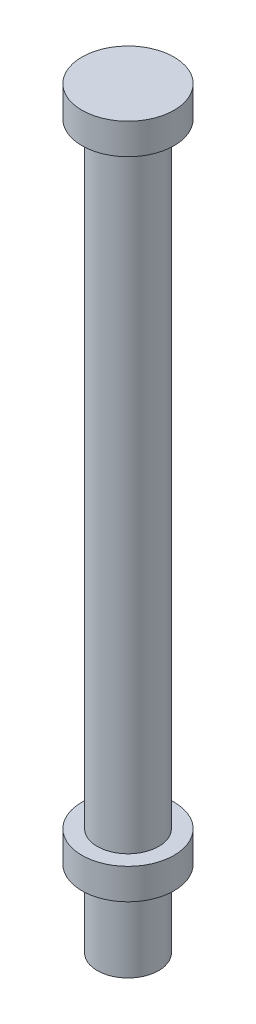
SolidWorks part; units mm, degrees
material "6061 Alloy"
ref_plane "Front Plane" through (0, 0, 0) normal (0, 0, 1) x (1, 0, 0)
ref_plane "Top Plane" through (0, 0, 0) normal (0, 1, 0) x (1, 0, 0)
ref_plane "Right Plane" through (0, 0, 0) normal (1, 0, 0) x (0, 0, -1)
sketch "Sketch3" plane through (0, 0, 0) normal (0, 1, 0) x (1, 0, 0)
  circle A0 centre (0, 0) radius 20
  dimension "D1" = 40
extrude "Boss-Extrude4" add sketch "Sketch3" along normal blind 400
sketch "Sketch13" plane through (0, 400, 0) normal (0, 1, 0) x (1, 0, 0)
  circle A2 centre (0, 0) radius 30
  circle A3 centre (0, 0) radius 30
  dimension "D1" = 10
extrude "Boss-Extrude5" add sketch "Sketch13" along normal blind 20
sketch "Sketch14" plane through (0, 0, 0) normal (0, -1, 0) x (1, 0, 0)
  circle A8 centre (0, 0) radius 30
  circle A9 centre (0, 0) radius 30
  dimension "D1" = 10
extrude "Boss-Extrude6" add sketch "Sketch14" along normal blind 20
sketch "Sketch15" plane through (0, -20, 0) normal (0, -1, 0) x (1, 0, 0)
  circle A2 centre (0, 0) radius 20
  circle A3 centre (0, 0) radius 20
  dimension "D1" = 10
extrude "Boss-Extrude7" add sketch "Sketch15" along normal blind 50
sketch "Sketch16" plane through (0, 420, 0) normal (0, 1, 0) x (1, 0, 0)
  line L0 (0, 0) -> (30, 0) construction
  circle A0 centre (0, 0) radius 30 construction
  point P0 (0, 0)
ref_axis "Axis4" through (0, -70, 0) along (0, 1, 0)
sketch "Sketch17" plane through (0, -70, 0) normal (0, -1, 0) x (1, 0, 0)
  line L0 (0, 0) -> (20, 0) construction
  line L1 (0, 0) -> (30, 0) construction
  circle A0 centre (0, 0) radius 20 construction
  point P0 (0, 0)
